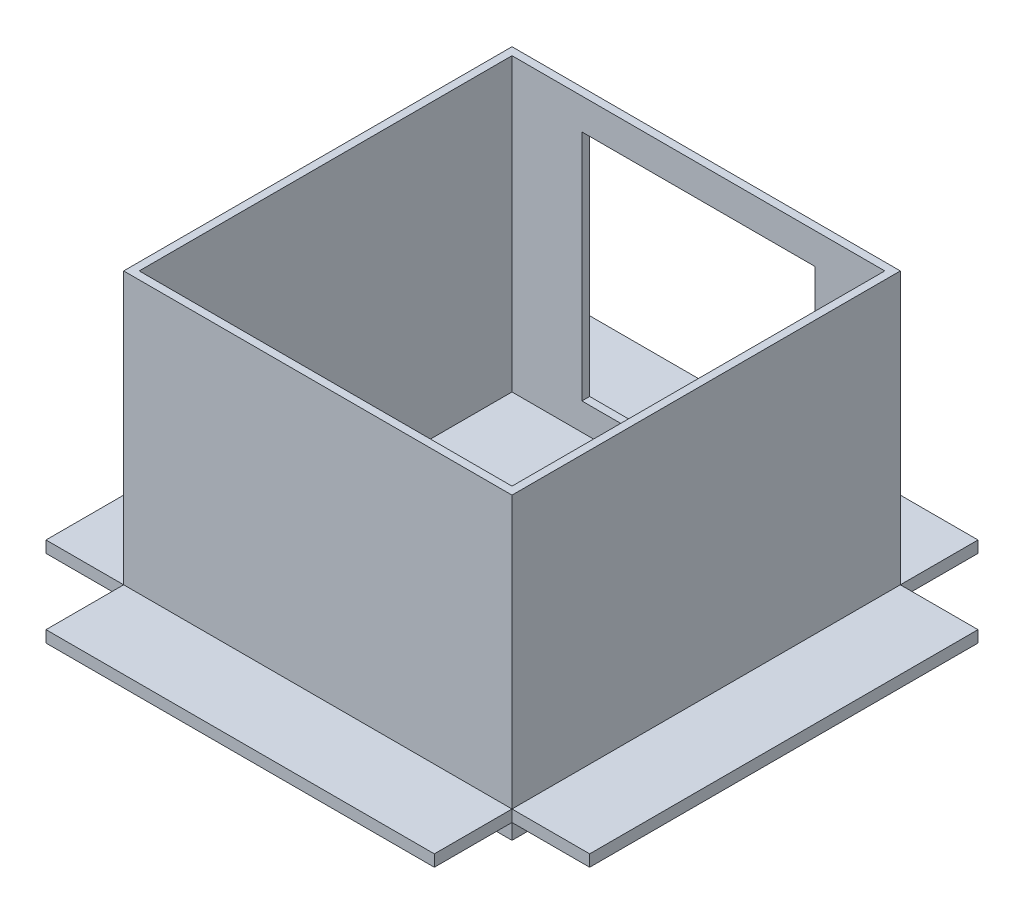
SolidWorks part; units mm, degrees
ref_plane "Front Plane" through (0, 0, 0) normal (0, 0, 1) x (1, 0, 0)
ref_plane "Top Plane" through (0, 0, 0) normal (0, 1, 0) x (1, 0, 0)
ref_plane "Right Plane" through (0, 0, 0) normal (1, 0, 0) x (0, 0, -1)
sketch "Sketch1" plane through (0, 0, 0) normal (0, 1, 0) x (1, 0, 0)
  line L12 (-50, 50) -> (-50, 70)
  line L13 (-50, 70) -> (-50, -70)
  line L14 (50, 0) -> (50, -70)
  line L15 (50, -70) -> (50, 70)
  line L17 (-70, -50) -> (-70, 50)
  line L18 (70, 0) -> (70, 50)
  line L19 (70, 50) -> (70, -50)
  line L20 (0, 50) -> (-70, 50)
  line L21 (-70, 50) -> (70, 50)
  line L22 (0, 70) -> (-50, 70)
  line L23 (-50, 70) -> (50, 70)
  line L24 (0, -50) -> (-70, -50)
  line L25 (-70, -50) -> (70, -50)
  line L26 (0, -70) -> (-50, -70)
  line L27 (-50, -70) -> (50, -70)
  dimension "D3" = 20
  dimension "D4" = 100
  dimension "D5" = 20
  dimension "D9" = 20
extrude "Boss-Extrude1" add sketch "Sketch1" along normal blind 3 contours L24 L25 L14 L15 L21 L20 L13 | L24 L13 L20 L17 | L26 L27 L15 L25 L24 L13 | L14 L25 L19 L18 L21 L15 | L23 L22 L12 L20 L21 L15 region at (0, 0, 0) region at (0, 0, -60) region at (-60, 0, 0) region at (0, 0, 60) region at (60, 0, 0)
sketch "Sketch2" plane through (0, 3, 0) normal (0, 1, 0) x (-1, 0, 0)
  line L0 (50, -50) -> (50, 50)
  line L1 (50, 50) -> (-50, 50)
  line L2 (-50, 50) -> (-50, -50)
  line L3 (-50, -50) -> (50, -50)
extrude "Boss-Extrude2" add sketch "Sketch2" along normal blind 70 and the other way blind 7
shell "Shell1" thickness 2 removed face at (0, 73, 0)
sketch "Sketch3" plane through (0, -4, 0) normal (0, -1, 0) x (1, 0, 0)
  line L0 (-40, 40) -> (40, 40)
  line L1 (40, 40) -> (40, 30)
  line L2 (40, 30) -> (-40, 30)
  line L3 (-40, 30) -> (-40, 40)
  line L4 (-48, -48) -> (-48, 48) construction
  line L5 (48, 48) -> (48, -48) construction
  line L6 (-48, 48) -> (48, 48) construction
  dimension "D1" = 8
  dimension "D2" = 8
  dimension "D3" = 8
  dimension "D4" = 10
extrude "Cut-Extrude1" cut sketch "Sketch3" against normal blind 11 contours L3 L2 L1 L0 region at (0, -4, 35)
sketch "Sketch6" plane through (0, 0, -50) normal (0, 0, -1) x (-1, 0, 0)
  line L0 (-30, 65) -> (30, 65)
  line L1 (30, 65) -> (30, 5)
  line L2 (30, 5) -> (-30, 5)
  line L3 (-30, 5) -> (-30, 65)
  line L5 (-50, 73) -> (50, 73) construction
  dimension "D1" = 60
  dimension "D2" = 60
  dimension "D3" = 8
  dimension "D4" = 20
extrude "Cut-Extrude2" cut sketch "Sketch6" against normal blind 2 contours L3 L2 L1 L0 region at (0, 35, -50)
